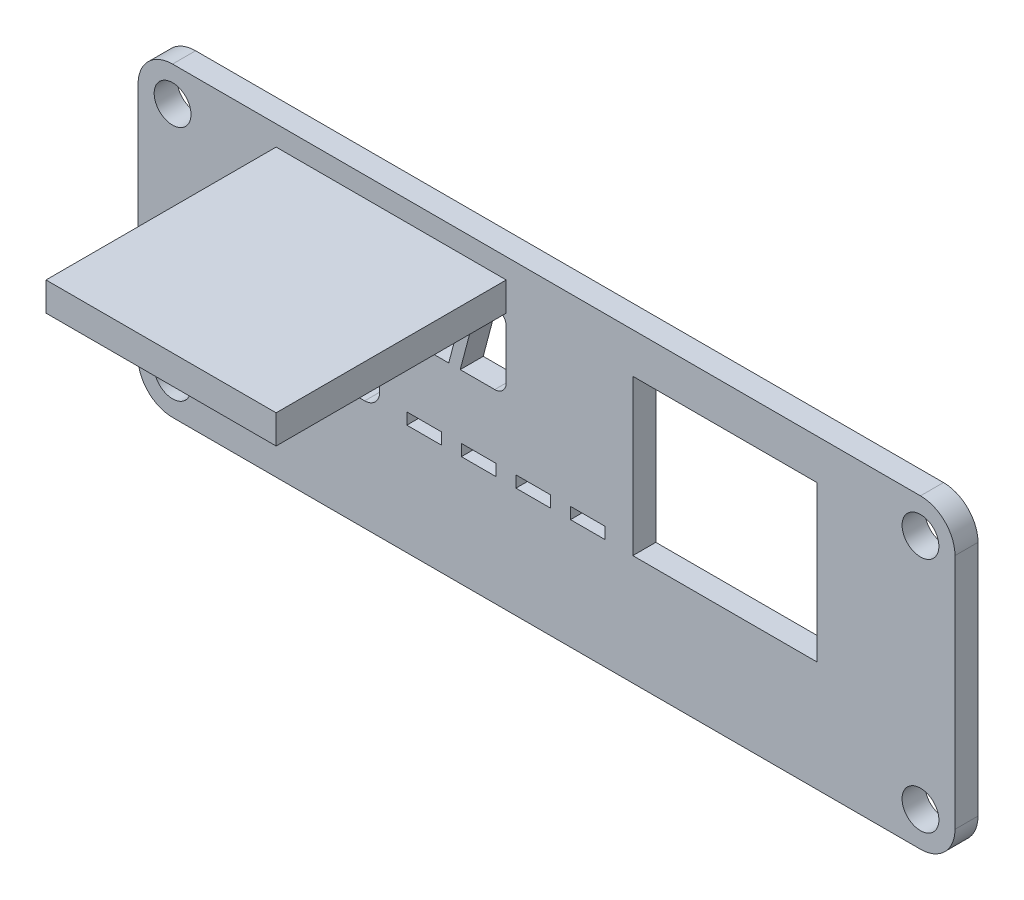
SolidWorks part; units mm, degrees
ref_plane "前视基准面" through (0, 0, 0) normal (0, 0, 1) x (1, 0, 0)
ref_plane "上视基准面" through (0, 0, 0) normal (0, 1, 0) x (1, 0, 0)
ref_plane "右视基准面" through (0, 0, 0) normal (1, 0, 0) x (0, 0, -1)
sketch "草图1" plane through (0, 0, 0) normal (0, 0, 1) x (1, 0, 0)
  line L1 (3, 0) -> (68, 0)
  line L2 (0, -3) -> (0, -23.6)
  line L3 (3, -26.6) -> (68, -26.6)
  line L4 (71, -3) -> (71, -23.6)
  arc A0 (0, -23.6) -> (3, -26.6) centre (3, -23.6) ccw
  arc A1 (68, -26.6) -> (71, -23.6) centre (68, -23.6) ccw
  arc A2 (68, 0) -> (71, -3) centre (68, -3) cw
  arc A3 (3, 0) -> (0, -3) centre (3, -3) ccw
  circle A4 centre (3, -3) radius 1.6
  circle A5 centre (68, -3) radius 1.6
  circle A6 centre (68, -23.6) radius 1.6
  circle A7 centre (3, -23.6) radius 1.6
  point P9 (71, -26.6)
  point P12 (71, 0)
  point P15 (0, 0)
  dimension "D3" = 3
  dimension "D1" = 71
  dimension "D2" = 26.6
extrude "凸台-拉伸1" add sketch "草图1" along normal blind 2
sketch "草图2" plane through (0, 0, 0) normal (0, 0, -1) x (-1, 0, 0)
  line L0 (-71, -23.6) -> (-71, -3) construction
  line L1 (-59, -3.5) -> (-43, -3.5)
  line L2 (-59, -3.5) -> (-59, -17)
  line L3 (-59, -17) -> (-43, -17)
  line L4 (-43, -3.5) -> (-43, -17)
  line L5 (-68, 0) -> (-3, 0) construction
  line L6 (0, -3) -> (0, -23.6) construction
  line L7 (-19.7, -17) -> (-13.1, -17)
  line L8 (-21, -15.7) -> (-21, -14.9)
  line L9 (-19.7, -13.6) -> (-13.1, -13.6)
  line L10 (-11.8, -15.7) -> (-11.8, -14.9)
  line L16 (-40.584, -16) -> (-37.584, -16)
  line L17 (-40.584, -16) -> (-40.584, -17)
  line L18 (-40.584, -17) -> (-37.584, -17)
  line L19 (-37.584, -16) -> (-37.584, -17)
  line L20 (-35.843, -16) -> (-32.843, -16)
  line L21 (-35.843, -16) -> (-35.843, -17)
  line L22 (-35.843, -17) -> (-32.843, -17)
  line L23 (-32.843, -16) -> (-32.843, -17)
  line L24 (-31.101, -16) -> (-28.101, -16)
  line L25 (-31.101, -16) -> (-31.101, -17)
  line L26 (-31.101, -17) -> (-28.101, -17)
  line L27 (-28.101, -16) -> (-28.101, -17)
  line L28 (-26.36, -16) -> (-23.36, -16)
  line L29 (-26.36, -16) -> (-26.36, -17)
  line L30 (-26.36, -17) -> (-23.36, -17)
  line L31 (-23.36, -16) -> (-23.36, -17)
  arc A0 (-19.7, -17) -> (-21, -15.7) centre (-19.7, -15.7) cw
  arc A1 (-13.1, -17) -> (-11.8, -15.7) centre (-13.1, -15.7) ccw
  arc A2 (-13.1, -13.6) -> (-11.8, -14.9) centre (-13.1, -14.9) cw
  arc A3 (-21, -14.9) -> (-19.7, -13.6) centre (-19.7, -14.9) cw
  point P34 (-11.8, -17)
  point P37 (-11.8, -13.6)
  point P40 (-21, -13.6)
  dimension "D9" = 1.3
  dimension "D1" = 12
  dimension "D2" = 28
  dimension "D3" = 13.5
  dimension "D4" = 3.5
  dimension "D5" = 9.2
  dimension "D6" = 3.4
  dimension "D7" = 17
  dimension "D8" = 21
  dimension "D12" = 3
  dimension "D14" = 3
  dimension "D16" = 3
  dimension "D17" = 3
extrude "切除-拉伸2" cut sketch "草图2" against normal blind 2
sketch "草图3" plane through (0, 0, 2) normal (0, 0, 1) x (1, 0, 0)
  line L0 (68, 0) -> (3, 0) construction
  line L1 (12, -1.75) -> (32, -1.75)
  line L2 (12, -1.75) -> (12, -4.25)
  line L3 (12, -4.25) -> (32, -4.25)
  line L4 (32, -1.75) -> (32, -4.25)
  line L5 (0, -3) -> (0, -23.6) construction
  dimension "D1" = 20
  dimension "D2" = 2.5
  dimension "D3" = 1.75
  dimension "D4" = 12
  dimension "D5" = 11
extrude "凸台-拉伸2" add sketch "草图3" along normal blind 20
sketch "草图5" plane through (0, 0, 2) normal (0, 0, 1) x (1, 0, 0)
  line L0 (16, -4.25) -> (14.3472, -10.5)
  line L1 (13, -4.25) -> (31, -4.25)
  line L2 (12, -5.25) -> (12, -9.5)
  line L3 (13, -10.5) -> (31, -10.5)
  line L4 (32, -5.25) -> (32, -9.5)
  line L5 (16, -4.25) -> (17, -4.25)
  line L6 (12, -4.25) -> (32, -4.25) construction
  line L7 (14.3472, -10.5) -> (15.3472, -10.5)
  line L8 (12, -1.75) -> (12, -4.25) construction
  line L9 (17, -4.25) -> (15.3472, -10.5)
  line L10 (12, -4.25) -> (32, -4.25) construction
  line L11 (22.325, -4.25) -> (20.6722, -10.5)
  line L12 (22.325, -4.25) -> (23.325, -4.25)
  line L13 (20.6722, -10.5) -> (21.6722, -10.5)
  line L14 (23.325, -4.25) -> (21.6722, -10.5)
  line L15 (28.6528, -4.25) -> (27, -10.5)
  line L16 (28.6528, -4.25) -> (29.6528, -4.25)
  line L17 (27, -10.5) -> (28, -10.5)
  line L18 (29.6528, -4.25) -> (28, -10.5)
  arc A0 (31, -4.25) -> (32, -5.25) centre (31, -5.25) cw
  arc A1 (31, -10.5) -> (32, -9.5) centre (31, -9.5) ccw
  arc A2 (12, -9.5) -> (13, -10.5) centre (13, -9.5) ccw
  arc A3 (13, -4.25) -> (12, -5.25) centre (13, -5.25) ccw
  point P8 (17.913, -4.25)
  point P11 (32, -4.25)
  point P16 (12, -10.5)
  point P19 (12, -4.25)
  line M61 (32, -4.25) -> (12, -4.25)
  dimension "D3" = 1
  dimension "D1" = 6.25
  dimension "D2" = 20
  dimension "D4" = 1
  dimension "D5" = 3
  dimension "D6" = 18
  dimension "D7" = 3
  dimension "D8" = 1
  dimension "D9" = 6.325
  dimension "D10" = 6.3278
extrude "切除-拉伸3" cut sketch "草图5" against normal blind 20 contours A3 L2 A2 L3 L0 M61 | L11 L1 L9 L3 | L15 L1 L14 L3 | L3 A1 L4 A0 L18 M61 region at (13.6536, -7.0978, 2) region at (18.8361, -7.375, 2) region at (25.1625, -7.375, 2) region at (30.3464, -7.6522, 2)
